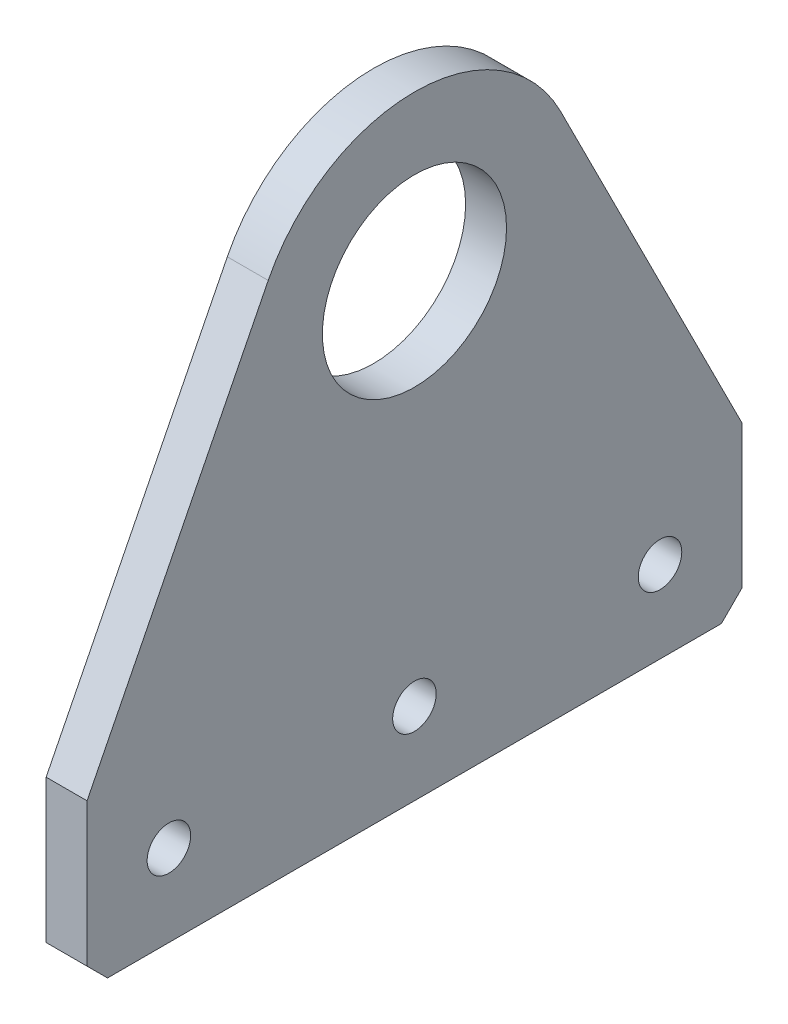
SolidWorks part; units mm, degrees
material "6061-T6 (SS)"
ref_plane "Front Plane" through (0, 0, 0) normal (0, 0, 1) x (1, 0, 0)
ref_plane "Top Plane" through (0, 0, 0) normal (0, 1, 0) x (1, 0, 0)
ref_plane "Right Plane" through (0, 0, 0) normal (1, 0, 0) x (0, 0, -1)
sketch "Sketch1" plane through (0, 0, 0) normal (1, 0, 0) x (0, 0, -1)
  line L0 (0, 0) -> (0, 25.4)
  line L1 (0, 25.4) -> (28.1104, 81.2667)
  line L2 (73.4896, 81.2667) -> (101.6, 25.4)
  line L3 (101.6, 25.4) -> (101.6, 0)
  line L4 (101.6, 0) -> (0, 0)
  arc A0 (28.1104, 81.2667) -> (73.4896, 81.2667) centre (50.8, 69.85) cw
  circle A1 centre (50.8, 69.85) radius 14.2875
  dimension "D3" = 28.575
  dimension "D4" = 25.4
  dimension "D5" = 69.85
  dimension "D1" = 101.6
  dimension "D2" = 25.4
extrude "Boss-Extrude1" add sketch "Sketch1" along normal blind 6.35
sketch "Sketch2" plane through (6.35, 0, 0) normal (1, 0, 0) x (0, 0, -1)
  line L0 (0, 25.4) -> (0, 0) construction
  line L1 (101.6, 0) -> (101.6, 25.4) construction
  line L2 (0, 0) -> (101.6, 0) construction
  line L3 (12.7, 12.7) -> (88.9, 12.7) construction
  circle A0 centre (12.7, 12.7) radius 3.3782
  circle A1 centre (50.8, 12.7) radius 3.3782
  circle A2 centre (88.9, 12.7) radius 3.3782
  dimension "D1" = 12.7
  dimension "D2" = 12.7
  dimension "D3" = 12.7
  dimension "D4" = 6.7564
extrude "Cut-Extrude1" cut sketch "Sketch2" against normal through all
chamfer "Chamfer1" distance 3.175 angle 45 2 edges at (3.175, 0, -101.6) (3.175, 0, 0)
